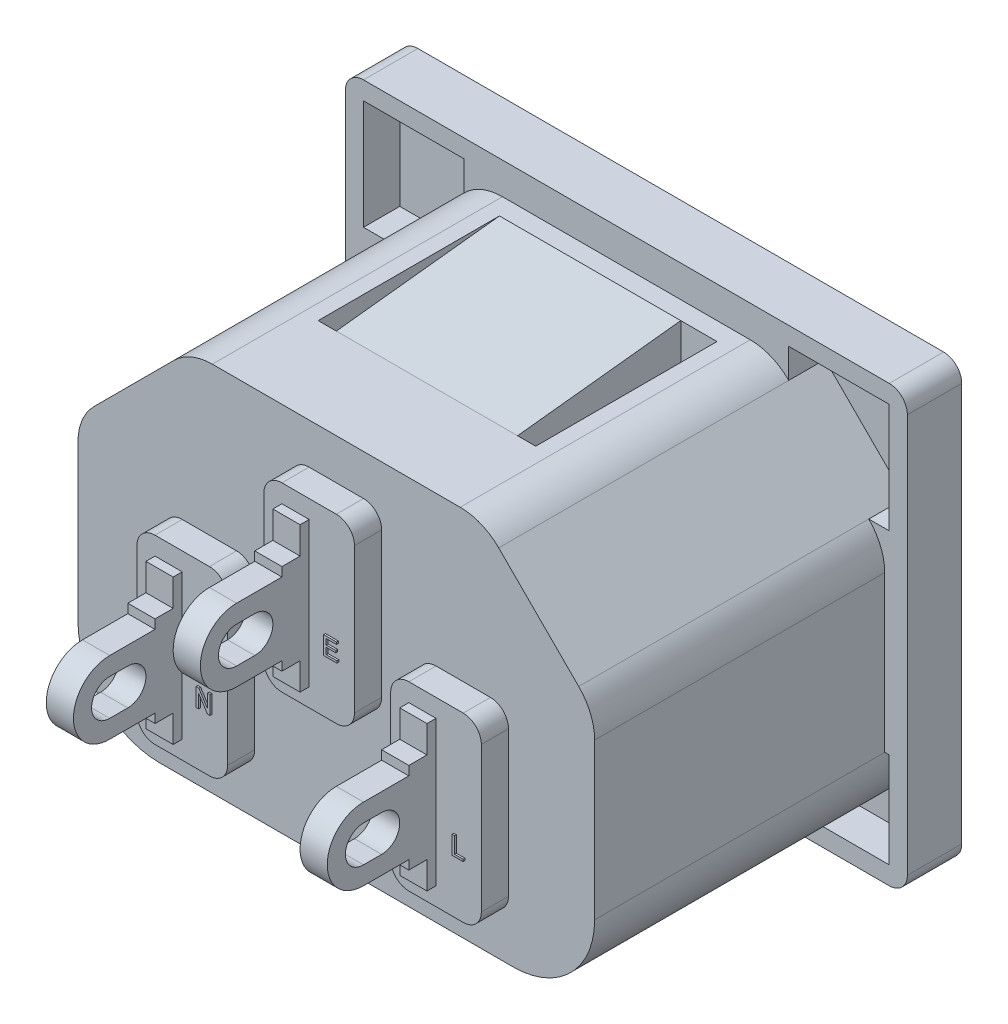
SolidWorks part; units mm, degrees
note: The reader was unsure of these and kept them because the rebuilt part matched: shared geometry of "草圖11<2>".
ref_plane "Front" through (0, 0, 0) normal (0, 0, 1) x (1, 0, 0)
ref_plane "Top" through (0, 0, 0) normal (0, 1, 0) x (1, 0, 0)
ref_plane "Right" through (0, 0, 0) normal (1, 0, 0) x (0, 0, -1)
sketch "草圖1" plane through (0, 0, 0) normal (0, 0, 1) x (1, 0, 0)
  line L0 (-15.5, 0) -> (15.5, 0) construction
  line L1 (-15.5, 12) -> (15.5, 12)
  line L2 (-15.5, 12) -> (-15.5, -12)
  line L3 (-15.5, -12) -> (15.5, -12)
  line L4 (15.5, 12) -> (15.5, -12)
  dimension "D1" = 24
  dimension "D2" = 31
extrude "Feature" add sketch "草圖1" along normal blind 18.3
sketch "草圖2" plane through (0, 0, 0) normal (0, 0, -1) x (-1, 0, 0)
  line L0 (-7.25, 8.25) -> (7.25, 8.25)
  line L1 (7.25, 8.25) -> (12.25, 3.25)
  line L2 (12.25, 3.25) -> (12.25, -8.25)
  line L3 (12.25, -8.25) -> (-12.25, -8.25)
  line L4 (-12.25, -8.25) -> (-12.25, 3.25)
  line L5 (-12.25, 3.25) -> (-7.25, 8.25)
  line L8 (0, 8.25) -> (0, -8.25) construction
  dimension "D1" = 24.5
  dimension "D2" = 16.5
  dimension "D3" = 5
  dimension "D4" = 5
extrude "Feature1" cut sketch "草圖2" against normal blind 17
fillet "Feature2" radius 2.5 2 edges at (-12.25, -8.25, 8.5) (12.25, -8.25, 8.5)
fillet "Feature3" radius 1 4 edges at (-12.25, 3.25, 8.5) (-7.25, 8.25, 8.5) (12.25, 3.25, 8.5) (7.25, 8.25, 8.5)
shell "Feature4" thickness 2
sketch "草圖3" plane through (0, 10.25, 0) normal (0, 1, 0) x (1, 0, 0)
  line L0 (-6, -14) -> (-5, -14)
  line L1 (-5, -14) -> (-5, -5)
  line L2 (-5, -5) -> (5, -5)
  line L3 (5, -5) -> (5, -14)
  line L4 (5, -14) -> (6, -14)
  line L5 (6, -14) -> (6, -4)
  line L6 (6, -4) -> (-6, -4)
  line L7 (-6, -4) -> (-6, -14)
  line L8 (15.5, 0) -> (-15.5, 0) construction
  line L9 (0, -5) -> (0, -14) construction
  dimension "D1" = 10
  dimension "D2" = 1
  dimension "D3" = 4
  dimension "D4" = 1
  dimension "D5" = 10
extrude "Feature5" cut sketch "草圖3" against normal up to surface (2 mm away) up to face at (0, 8.25, 8.5)
sketch "草圖4" plane through (-5, 0, 0) normal (-1, 0, 0) x (0, 0, 1)
  line L0 (5, 10.25) -> (5, 11.25)
  line L1 (5, 11.25) -> (14, 10.25)
  line L2 (5, 10.25) -> (14, 10.25)
  dimension "D1" = 1
extrude "Feature6" add sketch "草圖4" against normal up to surface (10 mm away) up to face at (5, 9.25, 9.5)
sketch "草圖5" plane through (0, 8.25, 0) normal (0, -1, 0) x (1, 0, 0)
  line L0 (-6, 4) -> (-6, 14) construction
  line L1 (-6, 9) -> (-5, 9)
  line L2 (-6, 9) -> (-6, 11)
  line L3 (-6, 11) -> (-5, 11)
  line L4 (-5, 9) -> (-5, 11)
  line L5 (-5, 14) -> (-5, 5) construction
  line L6 (5, 5) -> (5, 14) construction
  line L7 (5, 9) -> (6, 9)
  line L8 (5, 9) -> (5, 11)
  line L9 (5, 11) -> (6, 11)
  line L10 (6, 9) -> (6, 11)
  line L11 (6, 14) -> (6, 4) construction
  line L12 (-6, 14) -> (-5, 14) construction
  dimension "D1" = 3
  dimension "D2" = 2
extrude "Feature7" add sketch "草圖5" against normal blind 0.5
sketch "草圖7" plane through (0, 0, 19) normal (0, 0, 1) x (1, 0, 0)
  line L1 (-2.5, 8) -> (2.5, 8)
  line L2 (-2.5, 8) -> (-2.5, -2)
  line L3 (-2.5, -2) -> (2.5, -2)
  line L4 (2.5, 8) -> (2.5, -2)
  line L5 (-9.5, 2) -> (-4.5, 2)
  line L6 (-9.5, 2) -> (-9.5, -8)
  line L7 (-9.5, -8) -> (-4.5, -8)
  line L8 (-4.5, 2) -> (-4.5, -8)
  line L9 (4.5, 2) -> (9.5, 2)
  line L10 (4.5, 2) -> (4.5, -8)
  line L11 (4.5, -8) -> (9.5, -8)
  line L12 (9.5, 2) -> (9.5, -8)
  dimension "D1" = 10
  dimension "D2" = 5
  dimension "D3" = 16
  dimension "D4" = 19
  dimension "D5" = 9.5
  dimension "D6" = 8
  dimension "D7" = 2.5
extrude "Feature8" add sketch "草圖7" along normal blind 1.5
fillet "Feature9" radius 1 16 edges at (9.5, -8, 19.75) (4.5, -8, 19.75) (9.5, 2, 19.75) (4.5, 2, 19.75) (-4.5, 2, 19.75) (-9.5, 2, 19.75) (-9.5, -8, 19.75) (-4.5, -8, 19.75) (-2.5, -2, 19.75) (-2.5, 8, 19.75) (2.5, 8, 19.75) (2.5, -2, 19.75) (15.5, -12, 1) (-15.5, -12, 1) (-15.5, 12, 1) (15.5, 12, 1)
sketch "草圖8" plane through (0, -10.25, 0) normal (0, -1, 0) x (1, 0, 0)
  line L0 (-9, 14) -> (-9, 5)
  line L1 (-9, 5) -> (-5, 5)
  line L2 (-5, 5) -> (-5, 14)
  line L3 (-5, 14) -> (-4.5, 14)
  line L4 (-4.5, 14) -> (-4.5, 4)
  line L5 (-4.5, 4) -> (-9.5, 4)
  line L6 (-9.5, 4) -> (-9.5, 14)
  line L7 (-9.5, 14) -> (-9, 14)
  line L8 (-14.5, 0) -> (14.5, 0) construction
  dimension "D1" = 4
  dimension "D2" = 0.5
  dimension "D3" = 0.5
  dimension "D4" = 1
  dimension "D5" = 4
  dimension "D6" = 10
  dimension "D7" = 9
extrude "Feature10" cut sketch "草圖8" against normal up to surface (2 mm away) up to face at (0, -8.25, 8.5)
sketch "草圖9" plane through (-5, 0, 0) normal (1, 0, 0) x (0, 0, -1)
  line L0 (-5, -10.25) -> (-5, -11.25)
  line L1 (-5, -11.25) -> (-16, -10.25)
  line L2 (-16, -10.25) -> (-5, -10.25)
  line L3 (-19, -5.75) -> (-19, -10.25) construction
  dimension "D1" = 3
  dimension "D2" = 1
extrude "Feature11" add sketch "草圖9" against normal blind 4
sketch "草圖10" plane through (0, -8.25, 0) normal (0, 1, 0) x (1, 0, 0)
  line L0 (-9, -16) -> (-9, -5) construction
  line L1 (-9, -9) -> (-9.5, -9)
  line L2 (-9, -9) -> (-9, -11)
  line L3 (-9, -11) -> (-9.5, -11)
  line L4 (-9.5, -9) -> (-9.5, -11)
  line L5 (-9.5, -14) -> (-9.5, -4) construction
  line L6 (-5, -16) -> (-5, -5) construction
  line L7 (-5, -9) -> (-4.5, -9)
  line L8 (-5, -9) -> (-5, -11)
  line L9 (-5, -11) -> (-4.5, -11)
  line L10 (-4.5, -9) -> (-4.5, -11)
  line L11 (-4.5, -4) -> (-4.5, -14) construction
  line L13 (-5, -11) -> (-6, -11) construction
  line L14 (-6, -9) -> (-5, -9) construction
extrude "Feature12" add sketch "草圖10" against normal blind 0.5
mirror "Feature13" about plane through (0, 0, 0) normal (1, 0, 0) of "Feature12", "Feature10", "Feature11"
sketch "草圖11" plane through (0, 0, 20.5) normal (0, 0, 1) x (1, 0, 0)
  line L0 (-9.5, -3) -> (-4.5, -3) construction
  line L1 (-8.5, -7) -> (-7, -7)
  line L2 (-8.5, -7) -> (-8.5, 1)
  line L3 (-8.5, 1) -> (-7, 1)
  line L4 (-7, -7) -> (-7, 1)
  line L5 (-9.5, 1) -> (-9.5, -7) construction
  line L6 (-4.5, -7) -> (-4.5, 1) construction
  line L7 (-2.5, 3) -> (2.5, 3) construction
  line L8 (-2.5, 7) -> (-2.5, -1) construction
  line L9 (2.5, -1) -> (2.5, 7) construction
  line L10 (4.5, -3) -> (9.5, -3) construction
  line L11 (4.5, 1) -> (4.5, -7) construction
  line L12 (9.5, -7) -> (9.5, 1) construction
  line L14 (-1.5, 7) -> (0, 7)
  line L15 (-1.5, 7) -> (-1.5, -1)
  line L16 (-1.5, -1) -> (0, -1)
  line L17 (0, 7) -> (0, -1)
  line L18 (5.5, 1) -> (7, 1)
  line L19 (5.5, 1) -> (5.5, -7)
  line L20 (5.5, -7) -> (7, -7)
  line L21 (7, 1) -> (7, -7)
  point P4 (-7, -3)
  point P31 (0, 3)
  point P32 (7, -3)
  dimension "D1" = 8
  dimension "D2" = 1.5
extrude "Feature14" add sketch "草圖11" along normal blind 6 and the other way blind 15.5 separate body
extrude "Feature15" cut sketch "草圖11<2>" against normal through all contours L4 L3 L2 L1 | L17 L16 L15 L14 | L21 L20 L19 L18
sketch "草圖11<2>" plane through (0, 0, 20.5) normal (0, 0, 1) x (1, 0, 0) same geometry as "草圖11"
sketch "草圖13" plane through (-7, 0, 0) normal (1, 0, 0) x (0, 0, -1)
  line L0 (-24.5, -1) -> (-22, -1)
  line L1 (-22, -1) -> (-22, -0.5)
  line L2 (-22, -0.5) -> (-21, -0.5)
  line L3 (-21, -0.5) -> (-21, 1)
  line L4 (-5, 1) -> (-26.5, 1) construction
  line L5 (-21, 1) -> (-26.5, 1)
  line L6 (-21, -7) -> (-21, -5.5)
  line L7 (-5, -7) -> (-26.5, -7) construction
  line L8 (-21, -5.5) -> (-22, -5.5)
  line L9 (-22, -5.5) -> (-22, -5)
  line L10 (-22, -5) -> (-24.5, -5)
  line L11 (-21, -7) -> (-26.5, -7)
  line L12 (-26.5, -7) -> (-26.5, 1)
  line L13 (-24.5, -4) -> (-23.5, -4)
  line L14 (-24.5, -2) -> (-23.5, -2)
  line L15 (-5, -3) -> (-26.5, -3) construction
  line L16 (-5, -7) -> (-17, -7)
  line L17 (-5, -7) -> (-5, -4)
  line L18 (-5, -4) -> (-17, -4)
  line L19 (-17, -7) -> (-17, -4)
  line L20 (-5, 1) -> (-17, 1)
  line L21 (-5, 1) -> (-5, 0)
  line L22 (-5, 0) -> (-17, 0)
  line L23 (-17, 1) -> (-17, 0)
  line L24 (-5, -7) -> (-5, 1) construction
  arc A0 (-24.5, -1) -> (-24.5, -5) centre (-24.5, -3) ccw
  arc A1 (-24.5, -2) -> (-24.5, -4) centre (-24.5, -3) ccw
  arc A2 (-23.5, -4) -> (-23.5, -2) centre (-23.5, -3) ccw
  line M1 (-5, 1) -> (-26.5, 1)
  line M2 (-26.5, 1) -> (-26.5, -7)
  line M3 (-26.5, -7) -> (-5, -7)
  line M4 (-5, -7) -> (-5, 1)
  dimension "D2" = 1
  dimension "D1" = 4
  dimension "D3" = 1
  dimension "D4" = 4.5
  dimension "D5" = 5
  dimension "D6" = 1
  dimension "D7" = 4
  dimension "D8" = 1
  dimension "D9" = 4
extrude "Feature16" cut sketch "草圖13" against normal through all contours A0 L0 L1 L2 L3 L12 M1 | L23 L22 M1 M4 | L19 L18 M3 M4 | A0 L6 L8 L9 L10 M2 M3 | L13 A2 L14 A1
chamfer "Feature17" distance 0.5 angle 60 4 edges at (-8.5, -2, 5) (-7, -2, 5) (-7.75, 0, 5) (-7.75, -4, 5)
sketch "草圖14" plane through (7, 0, 0) normal (1, 0, 0) x (0, 0, -1)
  line L0 (-24.5, -4) -> (-23.5, -4) construction
  line L1 (-24.5, -2) -> (-23.5, -2) construction
  line L2 (-24.5, -4) -> (-23.5, -4)
  line L3 (-24.5, -2) -> (-23.5, -2)
  line L4 (-5, -7) -> (-5, 1) construction
  line L5 (-5, 0) -> (-5, -4)
  line L10 (-5, 1) -> (-26.5, 1)
  line L11 (-26.5, 1) -> (-26.5, -7)
  line L12 (-26.5, -7) -> (-5, -7)
  line L13 (-5, -7) -> (-5, 1)
  line L14 (-5, 1) -> (-26.5, 1)
  line L15 (-17, -4) -> (-5.866, -4)
  line L16 (-5.866, -4) -> (-5.866, 0)
  line L17 (-5.866, 0) -> (-17, 0)
  line L18 (-17, 0) -> (-17, 1)
  line L19 (-17, 1) -> (-21, 1)
  line L20 (-21, 1) -> (-21, -0.5)
  line L21 (-21, -0.5) -> (-22, -0.5)
  line L22 (-22, -0.5) -> (-22, -1)
  line L23 (-22, -1) -> (-24.5, -1)
  line L24 (-24.5, -5) -> (-22, -5)
  line L25 (-22, -5) -> (-22, -5.5)
  line L26 (-22, -5.5) -> (-21, -5.5)
  line L27 (-21, -5.5) -> (-21, -7)
  line L28 (-21, -7) -> (-17, -7)
  line L29 (-17, -7) -> (-17, -4)
  line L30 (-17, -4) -> (-5, -4)
  line L31 (-26.5, 1) -> (-26.5, -7)
  line L32 (-5, 0) -> (-17, 0)
  line L33 (-17, 0) -> (-17, 1)
  line L34 (-26.5, -7) -> (-5, -7)
  line L35 (-21, 1) -> (-21, -0.5)
  line L36 (-21, -0.5) -> (-22, -0.5)
  line L37 (-22, -0.5) -> (-22, -1)
  line L38 (-22, -1) -> (-24.5, -1)
  line L39 (-24.5, -5) -> (-22, -5)
  line L40 (-22, -5) -> (-22, -5.5)
  line L41 (-22, -5.5) -> (-21, -5.5)
  line L42 (-21, -5.5) -> (-21, -7)
  line L43 (-5, -7) -> (-5, 1)
  line L44 (-17, -7) -> (-17, -4)
  arc A0 (-23.5, -4) -> (-23.5, -2) centre (-23.5, -3) ccw construction
  arc A1 (-24.5, -1) -> (-24.5, -5) centre (-24.5, -3) ccw
  arc A2 (-24.5, -1) -> (-24.5, -5) centre (-24.5, -3) ccw
  arc A3 (-24.5, -2) -> (-24.5, -4) centre (-24.5, -3) ccw construction
  arc A4 (-23.5, -4) -> (-23.5, -2) centre (-23.5, -3) ccw
  arc A5 (-24.5, -2) -> (-24.5, -4) centre (-24.5, -3) ccw
  line M21 (-5, 1) -> (-26.5, 1)
  line M22 (-26.5, 1) -> (-26.5, -7)
  line M23 (-26.5, -7) -> (-5, -7)
  line M24 (-5, -7) -> (-5, 1)
  dimension "D1" = 0
  dimension "D2" = 0
extrude "Feature18" cut sketch "草圖14" against normal through all contours A2 L38 L37 L36 L35 L31 M21 | L3 A5 L2 A4 | A2 L34 L42 L41 L40 L39 M22 | L44 L30 M23 M24 | L33 L32 M24 M21
chamfer "Feature19" distance 0.5 angle 60 4 edges at (7, -2, 5) (6.25, -4, 5) (5.5, -2, 5) (6.25, 0, 5)
sketch "草圖15" plane through (0, 0, 20.5) normal (0, 0, 1) x (1, 0, 0)
  line L0 (-7, -5) -> (-4.5, -5) construction
  line L1 (-7, -7) -> (-7, 1) construction
  line L2 (-4.5, -7) -> (-4.5, 1) construction
  line L3 (0, 1) -> (2.5, 1) construction
  line L6 (7, -5) -> (9.5, -5) construction
  line L7 (7, 1) -> (7, -7) construction
  line L8 (9.5, -7) -> (9.5, 1) construction
  line L9 (0, 7) -> (0, -1) construction
  line L10 (2.5, -1) -> (2.5, 7) construction
  line L11 (-8.5, -7) -> (-7, -7) construction
  line L12 (-1.5, -1) -> (0, -1) construction
  text T0 "N" font "Arial" height 1
  text T1 "L" font "Arial" height 1
  text T2 "E" font "Arial" height 1
  dimension "D1" = 2
  dimension "D2" = 2
extrude "Feature20" add sketch "草圖15" along normal blind 0.1
sketch "草圖16" plane through (0, 0, 0) normal (1, 0, 0) x (0, 0, -1)
  line L0 (-24.5, 5) -> (-22, 5)
  line L1 (-22, 5) -> (-22, 5.5)
  line L2 (-22, 5.5) -> (-21, 5.5)
  line L3 (-21, 5.5) -> (-21, 7)
  line L4 (-26.5, -1) -> (-26.5, 7) construction
  line L5 (-5, 7) -> (-26.5, 7) construction
  line L6 (-24.5, 1) -> (-22, 1)
  line L7 (-22, 1) -> (-22, 0.5)
  line L8 (-22, 0.5) -> (-21, 0.5)
  line L9 (-24.5, 4) -> (-23.5, 4)
  line L10 (-21, 0.5) -> (-21, -1)
  line L11 (-5, -1) -> (-26.5, -1) construction
  line L12 (-22, -5.5) -> (-22, -5) construction
  line L13 (-24.5, 2) -> (-23.5, 2)
  line L14 (-24.5, -2) -> (-23.5, -2) construction
  line L15 (-21, -7) -> (-21, -5.5) construction
  line L16 (-17, -7) -> (-17, -4) construction
  line L17 (-5, -1) -> (-17, -1)
  line L18 (-5, -1) -> (-5, 0.5)
  line L19 (-5, 0.5) -> (-17, 0.5)
  line L20 (-17, -1) -> (-17, 0.5)
  line L21 (-5, 7) -> (-17, 7)
  line L22 (-5, 7) -> (-5, 4.5)
  line L23 (-5, 4.5) -> (-17, 4.5)
  line L24 (-17, 7) -> (-17, 4.5)
  arc A0 (-24.5, 5) -> (-24.5, 1) centre (-24.5, 3) ccw
  arc A1 (-24.5, 4) -> (-24.5, 2) centre (-24.5, 3) ccw
  arc A2 (-23.5, 2) -> (-23.5, 4) centre (-23.5, 3) ccw
  arc A3 (-24.5, -2) -> (-24.5, -4) centre (-24.5, -3) ccw construction
  line M1 (-5, 7) -> (-26.5, 7)
  line M2 (-26.5, 7) -> (-26.5, -1)
  line M3 (-26.5, -1) -> (-5, -1)
  line M4 (-5, -1) -> (-5, 7)
  dimension "D1" = 1.5
  dimension "D2" = 4
extrude "Feature21" cut sketch "草圖16" against normal through all contours A0 L0 L1 L2 L3 M1 M2 | L24 L23 M1 M4 | L20 L19 M3 M4 | A0 L10 L8 L7 L6 M2 M3 | L13 A2 L9 A1
chamfer "Feature22" distance 0.5 angle 60 4 edges at (-0.75, 0.5, 5) (-1.5, 2.5, 5) (-0.75, 4.5, 5) (0, 2.5, 5)
sketch "草圖19" plane through (0, 0, 2) normal (0, 0, 1) x (1, 0, 0)
  line L4 (-14.5, -12) -> (14.5, -12)
  line L5 (15.5, -11) -> (15.5, 11)
  line L6 (14.5, 12) -> (-14.5, 12)
  line L7 (-15.5, 11) -> (-15.5, -11)
  line L8 (-14.5, -12) -> (14.5, -12)
  line L9 (15.5, -11) -> (15.5, 11)
  line L10 (14.5, 12) -> (-14.5, 12)
  line L11 (-15.5, 11) -> (-15.5, -11)
  line L14 (-14.25, 2.8358) -> (-14.25, -5.75)
  line L15 (-9.75, -10.25) -> (9.75, -10.25)
  line L16 (14.25, -5.75) -> (14.25, 2.8358)
  line L17 (13.3713, 4.9571) -> (8.9571, 9.3713)
  line L18 (6.8358, 10.25) -> (-6.8358, 10.25)
  line L19 (-8.9571, 9.3713) -> (-13.3713, 4.9571)
  line L20 (-14.25, 2.8358) -> (-14.25, -5.75)
  line L21 (-9.75, -10.25) -> (9.75, -10.25)
  line L22 (14.25, -5.75) -> (14.25, 2.8358)
  line L23 (13.3713, 4.9571) -> (8.9571, 9.3713)
  line L24 (6.8358, 10.25) -> (-6.8358, 10.25)
  line L25 (-8.9571, 9.3713) -> (-13.3713, 4.9571)
  arc A4 (14.5, -12) -> (15.5, -11) centre (14.5, -11) ccw
  arc A5 (15.5, 11) -> (14.5, 12) centre (14.5, 11) ccw
  arc A6 (-14.5, 12) -> (-15.5, 11) centre (-14.5, 11) ccw
  arc A7 (-15.5, -11) -> (-14.5, -12) centre (-14.5, -11) ccw
  arc A8 (14.5, -12) -> (15.5, -11) centre (14.5, -11) ccw
  arc A9 (15.5, 11) -> (14.5, 12) centre (14.5, 11) ccw
  arc A10 (-14.5, 12) -> (-15.5, 11) centre (-14.5, 11) ccw
  arc A11 (-15.5, -11) -> (-14.5, -12) centre (-14.5, -11) ccw
  arc A14 (-14.25, -5.75) -> (-9.75, -10.25) centre (-9.75, -5.75) ccw
  arc A15 (9.75, -10.25) -> (14.25, -5.75) centre (9.75, -5.75) ccw
  arc A16 (14.25, 2.8358) -> (13.3713, 4.9571) centre (11.25, 2.8358) ccw
  arc A17 (8.9571, 9.3713) -> (6.8358, 10.25) centre (6.8358, 7.25) ccw
  arc A18 (-6.8358, 10.25) -> (-8.9571, 9.3713) centre (-6.8358, 7.25) ccw
  arc A19 (-13.3713, 4.9571) -> (-14.25, 2.8358) centre (-11.25, 2.8358) ccw
  arc A20 (-14.25, -5.75) -> (-9.75, -10.25) centre (-9.75, -5.75) ccw
  arc A21 (9.75, -10.25) -> (14.25, -5.75) centre (9.75, -5.75) ccw
  arc A22 (14.25, 2.8358) -> (13.3713, 4.9571) centre (11.25, 2.8358) ccw
  arc A23 (8.9571, 9.3713) -> (6.8358, 10.25) centre (6.8358, 7.25) ccw
  arc A24 (-6.8358, 10.25) -> (-8.9571, 9.3713) centre (-6.8358, 7.25) ccw
  arc A25 (-13.3713, 4.9571) -> (-14.25, 2.8358) centre (-11.25, 2.8358) ccw
  dimension "D1" = 0
  dimension "D2" = 0
extrude "Feature23" add sketch "草圖19" along normal blind 1
sketch "草圖18" plane through (0, 0, 3) normal (0, 0, 1) x (1, 0, 0)
  line L0 (8.9571, 9.3713) -> (8.9571, 11)
  line L1 (8.9571, 11) -> (14.5, 11)
  line L2 (-8.9571, 9.3713) -> (-8.9571, 11)
  line L3 (-8.9571, 11) -> (-14.5, 11)
  line L4 (-14.5, 11) -> (-14.5, 4.9571)
  line L5 (-14.5, 4.9571) -> (-13.3713, 4.9571)
  line L6 (-13.3713, 4.9571) -> (-8.9571, 9.3713) construction
  line L7 (14.5, 11) -> (14.5, 4.9571)
  line L8 (14.5, 4.9571) -> (13.3713, 4.9571)
  line L10 (14.25, -5.75) -> (14.5, -5.75)
  line L11 (14.5, -5.75) -> (14.5, -11)
  line L12 (14.5, -11) -> (9.75, -11)
  line L13 (9.75, -11) -> (9.75, -10.25)
  line L14 (-14.25, -5.75) -> (-14.5, -5.75)
  line L15 (-14.5, -5.75) -> (-14.5, -11)
  line L16 (-14.5, -11) -> (-9.75, -11)
  line L17 (-9.75, -11) -> (-9.75, -10.25)
  line L23 (14.5, 12) -> (-14.5, 12) construction
  line L24 (-15.5, 11) -> (-15.5, -11) construction
  line L25 (-14.5, -12) -> (14.5, -12) construction
  line L27 (15.5, -11) -> (15.5, 11) construction
  line L28 (8.9571, 9.3713) -> (13.3713, 4.9571) construction
  line L29 (-13.3713, 4.9571) -> (-8.9571, 9.3713)
  line L30 (8.9571, 9.3713) -> (13.3713, 4.9571)
  arc A0 (9.75, -10.25) -> (14.25, -5.75) centre (9.75, -5.75) ccw construction
  arc A3 (-14.25, -5.75) -> (-9.75, -10.25) centre (-9.75, -5.75) ccw construction
  arc A4 (9.75, -10.25) -> (14.25, -5.75) centre (9.75, -5.75) ccw
  arc A5 (-14.25, -5.75) -> (-9.75, -10.25) centre (-9.75, -5.75) ccw
  dimension "D1" = 1
  dimension "D2" = 1
  dimension "D3" = 1
  dimension "D4" = 1
extrude "Feature24" cut sketch "草圖18" against normal blind 2
